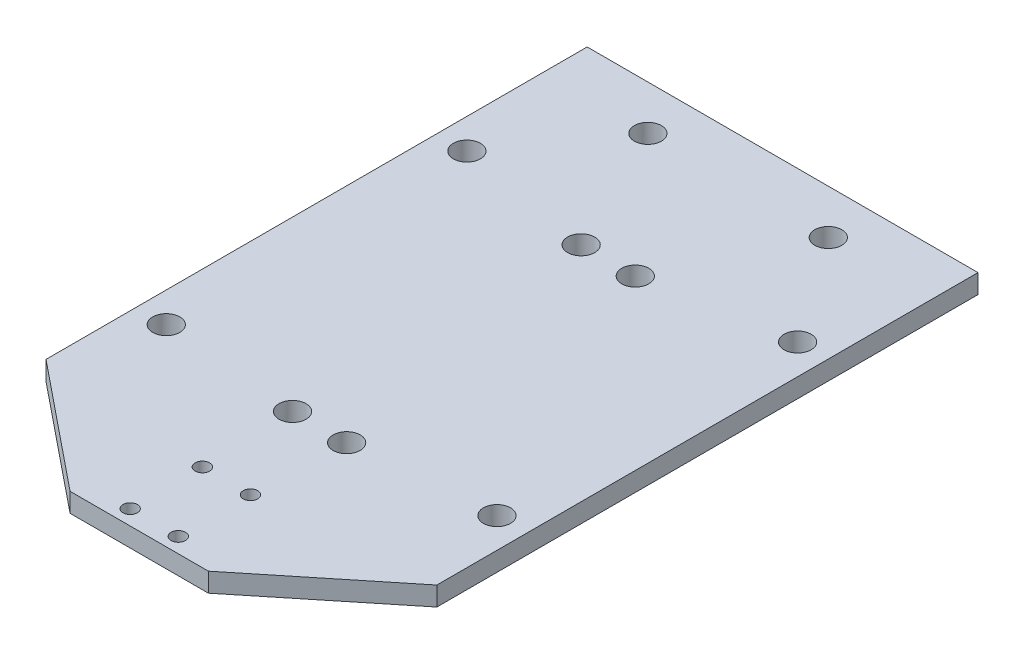
SolidWorks part; units mm, degrees
material "6061-T6 (SS)"
ref_plane "Front Plane" through (0, 0, 0) normal (0, 0, 1) x (1, 0, 0)
ref_plane "Top Plane" through (0, 0, 0) normal (0, 1, 0) x (1, 0, 0)
ref_plane "Right Plane" through (0, 0, 0) normal (1, 0, 0) x (0, 0, -1)
sketch "Sketch1" plane through (0, 0, 0) normal (0, 1, 0) x (1, 0, 0)
  line L0 (-11.5, -62) -> (-32.5, -45)
  line L1 (32.5, -45) -> (-32.5, -45)
  line L2 (32.5, -45) -> (32.5, 45)
  line L3 (32.5, 45) -> (-32.5, 45)
  line L4 (-32.5, -45) -> (-32.5, 45)
  line L5 (32.5, -45) -> (-32.5, 45) construction
  line L6 (32.5, 45) -> (-32.5, -45) construction
  line L7 (-11.5, -45) -> (11.5, -45)
  line L8 (-11.5, -45) -> (-11.5, -62)
  line L9 (-11.5, -62) -> (11.5, -62)
  line L10 (11.5, -45) -> (11.5, -62)
  line L11 (11.5, -62) -> (32.5, -45)
  line L12 (-32.5, -45) -> (32.5, -45)
  line L13 (11.5, -62) -> (-11.5, -62)
  point P0 (0, 0)
  point P10 (0, -62)
  dimension "D1" = 90
  dimension "D2" = 65
  dimension "D3" = 23
  dimension "D4" = 17
  dimension "D5" = 32.5
extrude "Boss-Extrude1" add sketch "Sketch1" along normal mid plane 3.175 contours L8 L1 L0 | L10 L11 L1 | L4 L1 L2 L3 | L10 L1 L8 L9 region at (-18.5, 0, 50.6667) region at (0, 0, 53.5) region at (0, 0, 0) region at (18.5, 0, 50.6667)
sketch "Sketch4" plane through (0, 1.5875, 0) normal (0, 1, 0) x (1, 0, 0)
  line L0 (-11.5, -62) -> (11.5, -62) construction
  point P0 (-4, -59.5)
  point P2 (4, -59.5)
  point P4 (4, -47.5)
  point P6 (-4, -47.5)
  point P16 (0, -62)
  dimension "D1" = 8
  dimension "D2" = 12
  dimension "D3" = 4
  dimension "D4" = 2.5
hole_wizard "M2 Clearance Hole1" positions "Sketch4" profile "Sketch3" hole size "M2" standard "ANSI Metric" end condition through all
sketch "Sketch3" plane through (-4, 1.5875, 59.5) normal (1, 0, 0) x (0, 0, 1)
  line L0 (0, 0) -> (0, 3.175)
  line L1 (0, 3.175) -> (1.2, 3.175)
  line L2 (1.2, 3.175) -> (1.2, 0)
  line L5 (1.2, 0) -> (0, 0)
  line L11 (0, -6.35) -> (0, 107.95) construction
  dimension "Thru Hole Dia." = 2.4
  dimension "Thru Hole Depth" = 3.175
sketch "Sketch7" plane through (0, 1.5875, 0) normal (0, 1, 0) x (1, 0, 0)
  line L0 (-32.5, -45) -> (-32.5, 45) construction
  line L1 (32.5, -45) -> (32.5, 45) construction
  line L2 (32.5, 45) -> (-32.5, 45) construction
  point P0 (-27.5, 20)
  point P2 (27.5, 20)
  point P4 (27.5, -30)
  point P6 (-27.5, -30)
  dimension "D1" = 5
  dimension "D2" = 5
  dimension "D3" = 25
  dimension "D4" = 50
hole_wizard "M4 Clearance Hole1" positions "Sketch7" profile "Sketch6" hole size "M4" standard "ANSI Metric" end condition through all
sketch "Sketch6" plane through (-27.5, 1.5875, -20) normal (1, 0, 0) x (0, 0, 1)
  line L0 (0, 0) -> (0, 3.175)
  line L1 (0, 3.175) -> (2.25, 3.175)
  line L2 (2.25, 3.175) -> (2.25, 0)
  line L5 (2.25, 0) -> (0, 0)
  line L11 (0, -6.35) -> (0, 107.95) construction
  dimension "Thru Hole Dia." = 4.5
  dimension "Thru Hole Depth" = 3.175
hole_wizard "M4 Clearance Hole2" positions "Sketch12" profile "Sketch9" hole size "M4" standard "ANSI Metric" end condition through all
sketch "Sketch12" plane through (0, 1.5875, 0) normal (0, 1, 0) x (1, 0, 0)
  line L0 (-11.5, -62) -> (11.5, -62) construction
  point P0 (-4.5, -32)
  point P2 (4.5, -32)
  point P4 (4.5, 16)
  point P6 (-4.5, 16)
  point P17 (0, -62)
  dimension "D1" = 48
  dimension "D2" = 9
  dimension "D3" = 4.5
  dimension "D4" = 30
sketch "Sketch9" plane through (-4.5, 1.5875, 32) normal (1, 0, 0) x (0, 0, 1)
  line L0 (0, 0) -> (0, 3.175)
  line L1 (0, 3.175) -> (2.25, 3.175)
  line L2 (2.25, 3.175) -> (2.25, 0)
  line L5 (2.25, 0) -> (0, 0)
  line L11 (0, -6.35) -> (0, 107.95) construction
  dimension "Thru Hole Dia." = 4.5
  dimension "Thru Hole Depth" = 3.175
hole_wizard "M4 Clearance Hole3" positions "Sketch15" profile "Sketch14" hole size "M4" standard "ANSI Metric" end condition through all
sketch "Sketch15" plane through (0, 1.5875, 0) normal (0, 1, 0) x (1, 0, 0)
  point P0 (15, 37.6)
  point P3 (-15, 37.6)
sketch "Sketch14" plane through (15, 1.5875, -37.6) normal (1, 0, 0) x (0, 0, 1)
  line L0 (0, 0) -> (0, 3.175)
  line L1 (0, 3.175) -> (2.25, 3.175)
  line L2 (2.25, 3.175) -> (2.25, 0)
  line L5 (2.25, 0) -> (0, 0)
  line L11 (0, -6.35) -> (0, 107.95) construction
  dimension "Thru Hole Dia." = 4.5
  dimension "Thru Hole Depth" = 3.175
